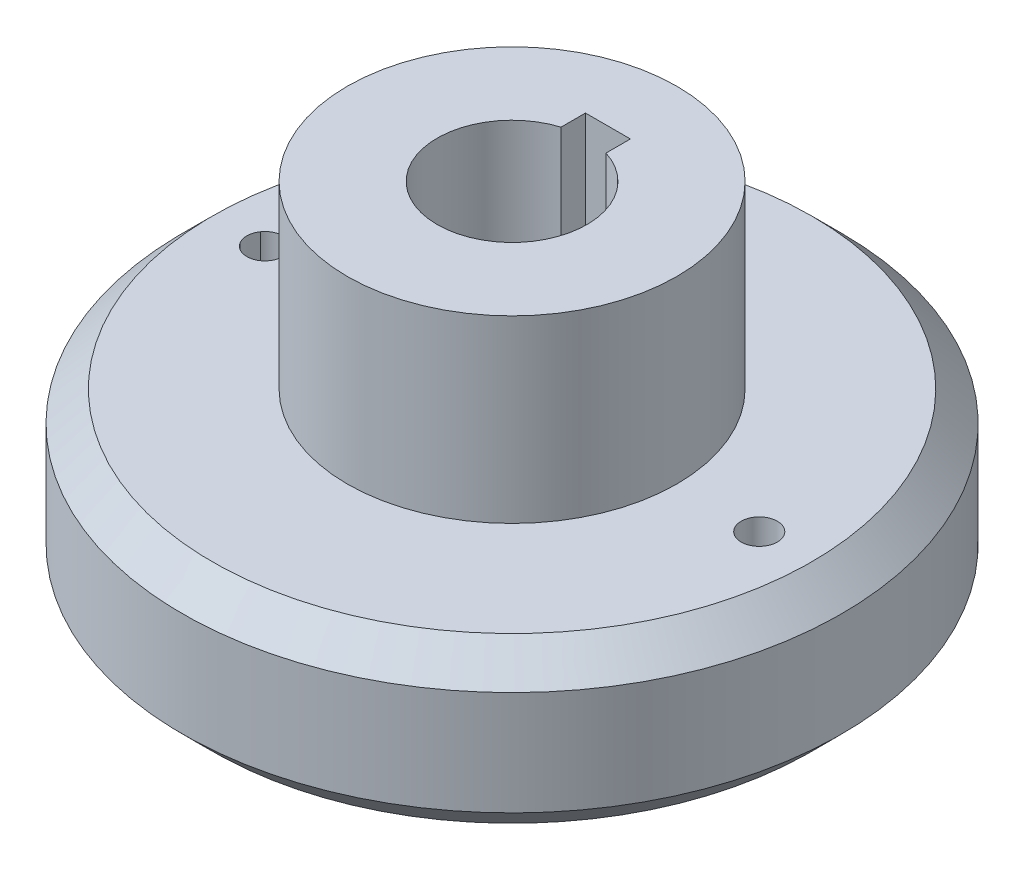
SolidWorks part; units mm, degrees
ref_plane "Front" through (0, 0, 0) normal (0, 0, 1) x (1, 0, 0)
ref_plane "Top" through (0, 0, 0) normal (0, 1, 0) x (1, 0, 0)
ref_plane "Right" through (0, 0, 0) normal (1, 0, 0) x (0, 0, -1)
sketch "Эскиз1" plane through (0, 0, 0) normal (0, 0, 1) x (1, 0, 0)
  line L0 (0, 0) -> (0, 6.9221) construction
  line L1 (5, 23) -> (5, 0)
  line L2 (5, 0) -> (17.5, 0)
  line L3 (17.5, 0) -> (17.5, 11)
  line L4 (17.5, 11) -> (11, 11)
  line L5 (11, 11) -> (11, 23)
  line L6 (11, 23) -> (5, 23)
  dimension "D1" = 35
  dimension "D2" = 10
  dimension "D3" = 23
  dimension "D4" = 12
  dimension "D5" = 22
revolve "Повернуть1" add sketch "Эскиз1" angle 360 about L0
sketch "Эскиз2" plane through (0, 0, 0) normal (0, 0, 1) x (1, 0, 0)
  line L3 (1.5, -27.4214) -> (-1.5, -27.4214)
  line L4 (1.5, -27.4214) -> (1.5, 27.4214)
  line L5 (1.5, 27.4214) -> (-1.5, 27.4214)
  line L6 (-1.5, -27.4214) -> (-1.5, 27.4214)
  line L7 (1.5, -27.4214) -> (-1.5, 27.4214) construction
  line L8 (1.5, 27.4214) -> (-1.5, -27.4214) construction
  point P0 (0, 0)
  dimension "D1" = 3
extrude "Вырез-Вытянуть1" cut sketch "Эскиз2" against normal blind 6.4
sketch "Эскиз3" plane through (0, 0, 0) normal (0, 0, 1) x (1, 0, 0)
  line L0 (0, 0) -> (0, 23.7771) construction
  line L1 (17.5, 0.0001) -> (17.5, 10.9999)
  line L2 (17.5, 0) -> (17.5, 11) construction
  line L3 (17.5, 10.9999) -> (20, 10.9999)
  line L6 (20, 10.9999) -> (22, 8.9999)
  line L7 (19.9561, 0.0001) -> (22, 2.044)
  line L8 (22, 2.044) -> (22, 8.9999)
  line L11 (19.9561, 0.0001) -> (17.5, 0.0001)
  line L12 (17.5, 11) -> (-17.5, 11) construction
  dimension "D1" = 0.0001
  dimension "D2" = 0.0001
  dimension "D3" = 44
revolve "Повернуть-Тонкостенный1" add sketch "Эскиз3" angle 360 about L0 wall 0.0001
sketch "Эскиз4" plane through (0, 11, 0) normal (0, 1, 0) x (1, 0, 0)
  circle A0 centre (-16.5, 0) radius 1.204
  circle A1 centre (16.5, 0) radius 1.2068
  dimension "D1" = 16.5
  dimension "D2" = 16.5
extrude "Вырез-Вытянуть2" cut sketch "Эскиз4" against normal through all
